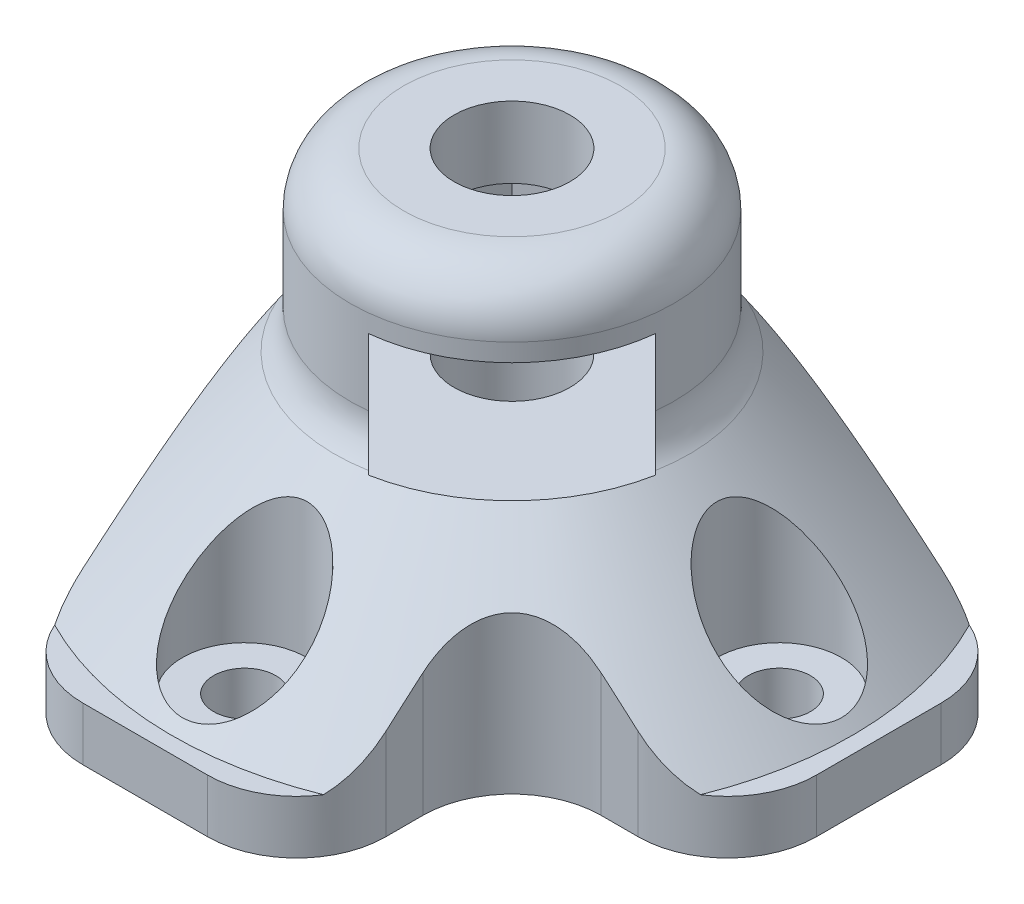
SolidWorks part; units mm, degrees
ref_plane "Plano frontal" through (0, 0, 0) normal (0, 0, 1) x (1, 0, 0)
ref_plane "Plano superior" through (0, 0, 0) normal (0, 1, 0) x (1, 0, 0)
ref_plane "Plano direito" through (0, 0, 0) normal (1, 0, 0) x (0, 0, -1)
sketch "Esboço2" plane through (0, 0, 0) normal (0, 1, 0) x (1, 0, 0)
  line L0 (0, 6.5818) -> (0, 9.0818) construction
  line L1 (0, 6.5818) -> (-5.7, 3.2909)
  line L2 (-5.7, 3.2909) -> (-5.7, -3.2909)
  line L3 (-5.7, -3.2909) -> (0, -6.5818)
  line L4 (0, -6.5818) -> (5.7, -3.2909)
  line L5 (5.7, -3.2909) -> (5.7, 3.2909)
  line L6 (5.7, 3.2909) -> (0, 6.5818)
  circle A0 centre (0, 0) radius 3.25
  circle A1 centre (0, 0) radius 9.0818
  circle A2 centre (0, 0) radius 5.7 construction
  dimension "D1" = 6.5
  dimension "D2" = 2.5
  dimension "D3" = 11.4
extrude "Ressalto-extrusão1" add sketch "Esboço2" along normal blind 22 contours L5 L6 L1 L2 L3 L4 A0 | A1 L6 L5 L4 L3 L2 L1 region at (2.7629, 0, -4.7855) region at (-8.8249, 0, 0)
sketch "Esboço3" plane through (0, 0, 0) normal (0, -1, 0) x (1, 0, 0)
  line L0 (-9.0818, 0) -> (-9.0818, 15)
  line L1 (0, -9.0818) -> (15, -9.0818)
  line L2 (20, -4.0818) -> (20, 2.9182)
  line L3 (15, 7.9182) -> (12.9182, 7.9182)
  line L4 (7.9182, 12.9182) -> (7.9182, 15)
  line L5 (2.9182, 20) -> (-4.0818, 20)
  line L6 (0, 0) -> (15, 0) construction
  line L7 (0, 0) -> (0, 15) construction
  circle A0 centre (0, 0) radius 9.0818 construction
  circle A2 centre (15, 0) radius 1.75
  circle A3 centre (0, 15) radius 1.75
  arc A4 (15, -9.0818) -> (20, -4.0818) centre (15, -4.0818) ccw
  arc A5 (20, 2.9182) -> (15, 7.9182) centre (15, 2.9182) ccw
  arc A6 (7.9182, 15) -> (2.9182, 20) centre (2.9182, 15) ccw
  arc A7 (-9.0818, 15) -> (-4.0818, 20) centre (-4.0818, 15) cw
  arc A8 (12.9182, 7.9182) -> (7.9182, 12.9182) centre (12.9182, 12.9182) cw
  arc A9 (-9.0818, 0) -> (0, -9.0818) centre (0, 0) ccw
  circle A10 centre (0, 0) radius 1.75
  point P16 (20, -9.0818)
  point P19 (20, 7.9182)
  point P24 (-9.0818, 20)
  circle M5 centre (0, 0) radius 9.0818
  circle M28 centre (0, 0) radius 3.25
  dimension "D4" = 3.5
  dimension "D5" = 15
  dimension "D6" = 5
  dimension "D7" = 5
  dimension "D1" = 20
  dimension "D2" = 20
  dimension "D3" = 17
extrude "Ressalto-extrusão2" add sketch "Esboço3" against normal blind 3 contours L3 A8 L4 A6 L5 A7 L0 L1 A4 L2 A5 A2 A3 M5 | M5 M28 | A10 M28 region at (0, 0, 8.8249) region at (-8.6705, 0, 7.5) region at (-3.1581, 0, 0)
chamfer "Chanfro1" distance 10 angle 45 1 edges at (6.4218, 3, 6.4218)
fillet "Filete1" radius 3 2 edges at (6.4218, 13, 6.4218) (0, 22, 9.0818)
sketch "Esboço4" plane through (0, 3, 0) normal (0, 1, 0) x (1, 0, 0)
  circle A0 centre (0, -15) radius 3.5
  circle A1 centre (15, 0) radius 3.5
  dimension "D1" = 7
extrude "Corte-extrusão2" cut sketch "Esboço4" along normal through all
ref_plane "Plano1" through (0, 18, 0) normal (0, 1, 0) x (1, 0, 0)
sketch "Esboço5" plane through (0, 18, 0) normal (0, 1, 0) x (1, 0, 0)
  line L0 (0, 0) -> (0, -15) construction
  line L1 (1.7035, 6.3575) -> (-4.654, 4.654)
  line L2 (-4.654, 4.654) -> (-6.3575, -1.7035)
  line L3 (-6.3575, -1.7035) -> (-1.7035, -6.3575)
  line L4 (-1.7035, -6.3575) -> (4.654, -4.654) construction
  line L5 (4.654, -4.654) -> (6.3575, 1.7035) construction
  line L6 (6.3575, 1.7035) -> (1.7035, 6.3575)
  line L7 (0, 0) -> (16.2437, -16.2437) construction
  line L8 (-1.7035, -6.3575) -> (5.9047, -13.9658)
  line L9 (5.9047, -13.9658) -> (13.9658, -5.9047)
  line L10 (13.9658, -5.9047) -> (6.3575, 1.7035)
  circle A0 centre (0, 0) radius 5.7 construction
  dimension "D1" = 11.4
  dimension "D2" = 45
extrude "Corte-extrusão3" cut sketch "Esboço5" against normal blind 6
